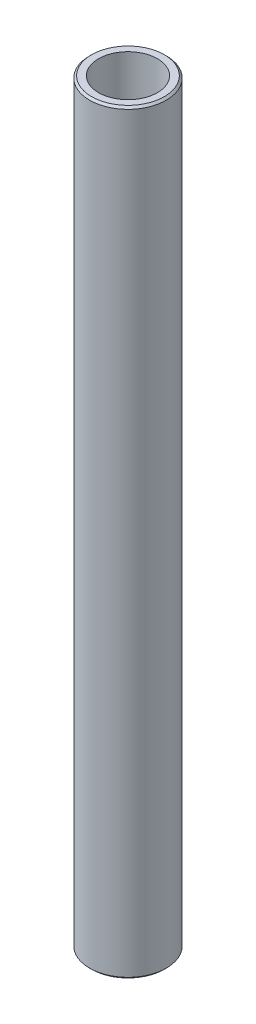
SolidWorks part; units mm, degrees
ref_plane "Front Plane" through (0, 0, 0) normal (0, 0, 1) x (1, 0, 0)
ref_plane "Top Plane" through (0, 0, 0) normal (0, 1, 0) x (1, 0, 0)
ref_plane "Right Plane" through (0, 0, 0) normal (1, 0, 0) x (0, 0, -1)
sketch "Sketch1" plane through (0, 0, 0) normal (0, 1, 0) x (1, 0, 0)
  circle A0 centre (0, 0) radius 30
  dimension "SHAFT_OD" = 60
extrude "Boss-Extrude1" add sketch "Sketch1" along normal blind 590.7718
sketch "Sketch2" plane through (0, 0, 0) normal (0, 1, 0) x (1, 0, 0)
  circle A0 centre (0, 0) radius 23.0093
  dimension "BORE_D" = 46.0186
extrude "Cut-Extrude1" cut sketch "Sketch2" along normal through all
chamfer "Chamfer1" distance 1.5851 angle 45 2 edges at (0, 590.7718, 30) (0, 0, 30)
